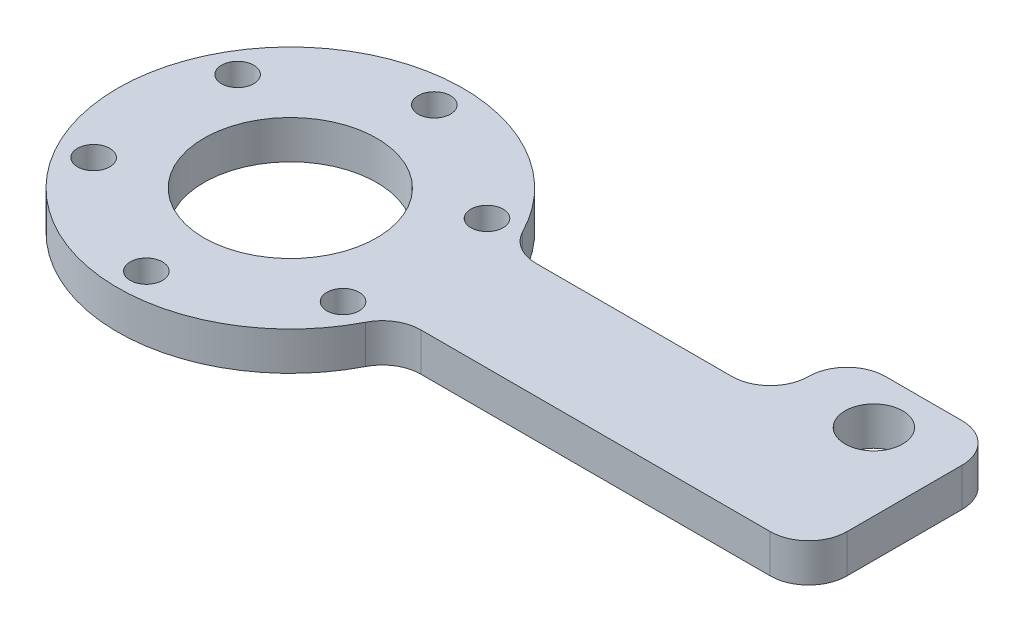
SolidWorks part; units mm, degrees
material "6063-T6"
ref_plane "Front" through (0, 0, 0) normal (0, 0, 1) x (1, 0, 0)
ref_plane "Top" through (0, 0, 0) normal (0, 1, 0) x (1, 0, 0)
ref_plane "Right" through (0, 0, 0) normal (1, 0, 0) x (0, 0, -1)
sketch "Sketch1" plane through (0, 0, 0) normal (0, 1, 0) x (1, 0, 0)
  circle A0 centre (0, 0) radius 14.2875
  circle A1 centre (0, 0) radius 28.575
  circle A2 centre (0, 0) radius 23.8125 construction
  circle A3 centre (0, 23.8125) radius 2.667
  circle A4 centre (20.6222, 11.9063) radius 2.667
  circle A5 centre (20.6222, -11.9062) radius 2.667
  circle A6 centre (0, -23.8125) radius 2.667
  circle A7 centre (-20.6222, -11.9063) radius 2.667
  circle A8 centre (-20.6222, 11.9062) radius 2.667
  point P19 (0, 0)
  dimension "D1" = 57.15
  dimension "D2" = 28.575
  dimension "D3" = 47.625
  dimension "D4" = 5.334
  dimension "D5" = 6
extrude "Boss-Extrude1" add sketch "Sketch1" along normal blind 6.35
sketch "Sketch2" plane through (0, 0, 0) normal (0, 1, 0) x (1, 0, 0)
  line L0 (0, 0) -> (14.2875, 0) construction
  line L5 (26.9408, -9.525) -> (95.25, -9.525)
  line L7 (26.9408, 9.525) -> (95.25, 9.525)
  line L8 (95.25, -9.525) -> (95.25, 9.525)
  line L9 (14.2875, 0) -> (95.25, 0) construction
  circle A4 centre (0, 0) radius 28.575 construction
  arc A5 (26.9408, -9.525) -> (26.9408, 9.525) centre (0, 0) ccw
  dimension "D1" = 95.25
extrude "Boss-Extrude2" add sketch "Sketch2" along normal up to surface (6.35 mm away) up to face at (-20.6222, 6.35, 14.5733)
sketch "Sketch3" plane through (0, 6.35, 0) normal (0, 1, 0) x (1, 0, 0)
  line L0 (0, 0) -> (82.55, 0) construction
  line L3 (95.25, 9.525) -> (69.85, 9.525)
  line L4 (95.25, 9.525) -> (95.25, 22.225)
  line L5 (95.25, 22.225) -> (69.85, 22.225)
  line L6 (69.85, 9.525) -> (69.85, 22.225)
  line L7 (95.25, 9.525) -> (69.85, 22.225) construction
  line L8 (95.25, 22.225) -> (69.85, 9.525) construction
  point P8 (82.55, 15.875)
  dimension "D2" = 22.225
  dimension "D3" = 25.4
  dimension "D1" = 82.55
extrude "Boss-Extrude3" add sketch "Sketch3" against normal up to surface (6.35 mm away) up to face at (47.2164, 0, 0)
sketch "Sketch4" plane through (0, 0, 0) normal (0, 1, 0) x (1, 0, 0)
  line L0 (0, 0) -> (82.55, 0) construction
  line L1 (82.55, 0) -> (82.55, 13.97) construction
  circle A0 centre (82.55, 13.97) radius 4.7625
  dimension "D3" = 9.525
  dimension "D1" = 82.55
  dimension "D2" = 13.97
extrude "Cut-Extrude4" cut sketch "Sketch4" along normal up to next
fillet "Fillet1" radius 6.35 6 edges at (69.85, 3.175, -9.525) (95.25, 3.175, 9.525) (69.85, 3.175, -22.225) (95.25, 3.175, -22.225) (26.9408, 3.175, 9.525) (26.9408, 3.175, -9.525)
